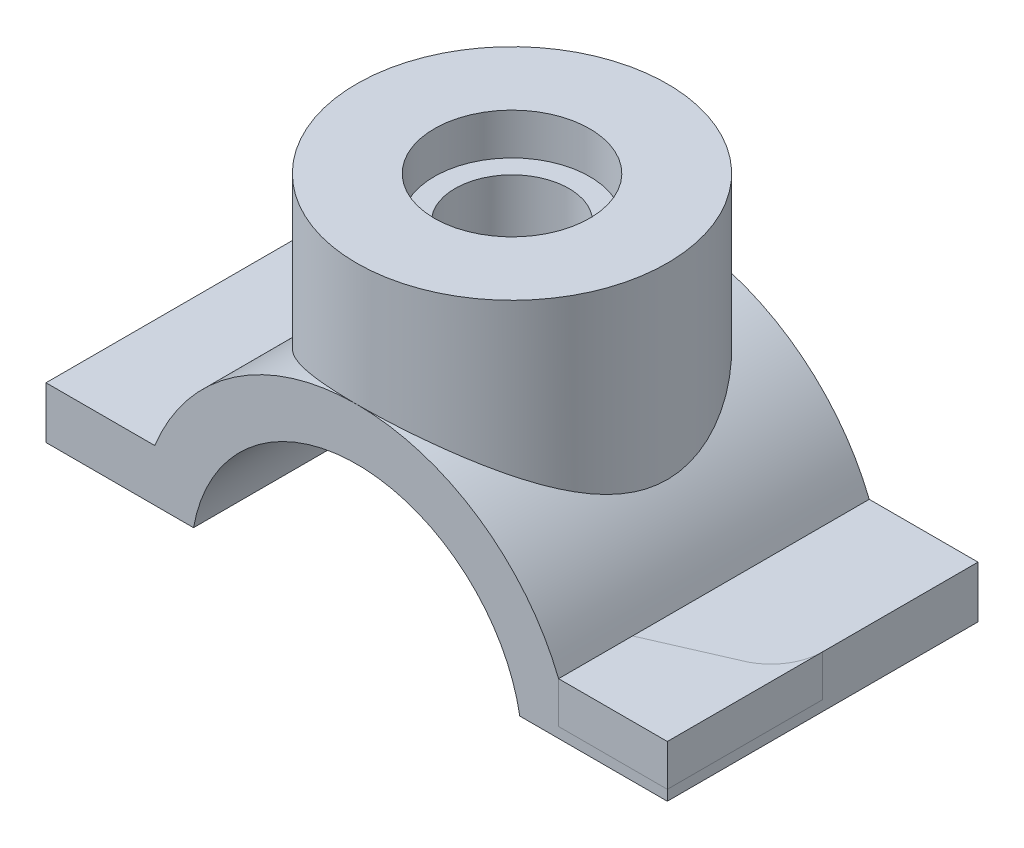
SolidWorks part; units mm, degrees
note: The reader was unsure of these and kept them because the rebuilt part matched: shared geometry of "Sketch2<10>", "Sketch2<11>".
ref_plane "Front Plane" through (0, 0, 0) normal (0, 0, 1) x (1, 0, 0)
ref_plane "Top Plane" through (0, 0, 0) normal (0, 1, 0) x (1, 0, 0)
ref_plane "Right Plane" through (0, 0, 0) normal (1, 0, 0) x (0, 0, -1)
sketch "Sketch1" plane through (0, 0, 0) normal (0, 0, 1) x (1, 0, 0)
  line L0 (-169.8338, 0) -> (-117.3223, 0)
  line L1 (77.6546, 0) -> (130.1662, 0)
  line L2 (-169.8338, -25) -> (-98.5993, -25)
  line L3 (58.9317, -25) -> (130.1662, -25)
  line L4 (-169.8338, 0) -> (-169.8338, -25)
  line L5 (130.1662, 0) -> (130.1662, -25)
  arc A0 (77.6546, 0) -> (-117.3223, 0) centre (-19.8338, -39) ccw
  arc A1 (58.9317, -25) -> (-98.5993, -25) centre (-19.8338, -39) ccw
  dimension "D2" = 39
  dimension "D4" = 105
  dimension "D1" = 300
  dimension "D3" = 25
extrude "Boss-Extrude2" add sketch "Sketch1" along normal mid plane 150
ref_plane "Plane2" through (0, 125, 0) normal (0, 1, 0) x (1, 0, 0)
sketch "Sketch2" plane through (0, 125, 0) normal (0, 1, 0) x (1, 0, 0)
  circle A1 centre (-19.8338, 0) radius 75
  circle A2 centre (-19.8338, 0) radius 37.5
  circle A3 centre (-19.8338, 0) radius 27.5
extrude "Boss-Extrude5" add sketch "Sketch2" against normal up to surface (59 mm away) contours A1 A2
extrude "Boss-Extrude6" add sketch "Sketch2<10>" against normal up to surface (59 mm away) contours A2 A3
sketch "Sketch2<10>" plane through (0, 125, 0) normal (0, 1, 0) x (1, 0, 0) same geometry as "Sketch2"
extrude "Cut-Extrude1" cut sketch "Sketch2<11>" against normal blind 20 contours A2 A3
sketch "Sketch2<11>" plane through (0, 125, 0) normal (0, 1, 0) x (1, 0, 0) same geometry as "Sketch2"
sketch "Sketch3" plane through (0, 0, 0) normal (0, 1, 0) x (1, 0, 0)
  line L0 (130.1662, -75) -> (130.1662, 75) construction
  line L1 (-169.8338, -75) -> (-169.8338, 75) construction
  line L2 (116.2762, -22.3957) -> (116.3922, -22.3378)
  line L3 (116.3922, -22.3378) -> (10.1879, -68.7291)
  line L4 (116.3922, 22.3378) -> (14.1034, 66.8825)
  line L5 (-154.8341, -22.9115) -> (-49.8345, -68.7383)
  line L6 (-154.8341, 22.9141) -> (-56.9404, 65.1775)
  circle A0 centre (105.1662, 0) radius 25
  circle A1 centre (-144.8338, 0.0013) radius 25
  arc A2 (14.1034, 66.8825) -> (-56.9404, 65.1775) centre (-19.8338, 0) ccw
  arc A3 (-49.8345, -68.7383) -> (10.1879, -68.7291) centre (-19.8338, 0) ccw
extrude "Cut-Extrude5" cut sketch "Sketch3" against normal blind 20 contours A0 L3 L1 L2 | A0 L3 L0 L1 L4
sketch "Sketch4" plane through (0, -20, 0) normal (0, 1, 0) x (1, 0, 0)
  line L0 (77.6546, 75) -> (77.6546, 39.2072)
  line L1 (77.6546, 39.2072) -> (113.8732, 23.4348)
  line L2 (130.1662, 0) -> (130.1662, 75)
  line L3 (130.1662, 75) -> (77.6546, 75)
  arc A0 (113.8732, 23.4348) -> (130.1662, 0) centre (103.0172, -1.4941) cw
extrude "Boss-Extrude7" add sketch "Sketch4" along normal blind 20
sketch "Sketch5" plane through (0, 0, 0) normal (0, 1, 0) x (1, 0, 0)
  line L0 (77.6546, -39.2588) -> (77.6546, -75)
  line L1 (77.6546, -75) -> (130.1662, -75)
  line L2 (130.1662, -75) -> (130.1662, 0)
  line L3 (113.9256, -23.4152) -> (77.6546, -39.2588)
  arc A0 (130.1662, 0) -> (113.9256, -23.4152) centre (105.1662, 0) cw
extrude "Boss-Extrude8" add sketch "Sketch5" against normal blind 20 separate body
